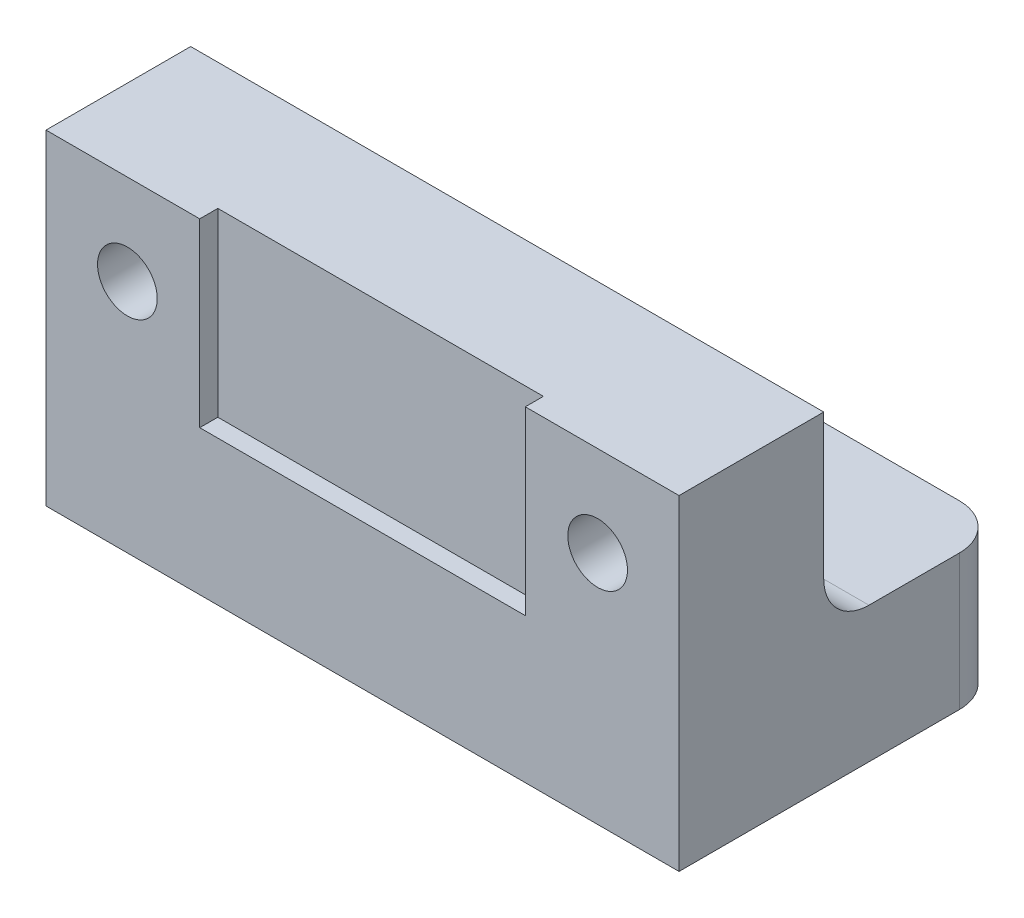
SolidWorks part; units mm, degrees
ref_plane "Front Plane" through (0, 0, 0) normal (0, 0, 1) x (1, 0, 0)
ref_plane "Top Plane" through (0, 0, 0) normal (0, 1, 0) x (1, 0, 0)
ref_plane "Right Plane" through (0, 0, 0) normal (1, 0, 0) x (0, 0, -1)
sketch "Sketch1" plane through (0, 0, 0) normal (0, 0, 1) x (1, 0, 0)
  line L1 (-17.5, -9) -> (17.5, -9)
  line L2 (-17.5, -9) -> (-17.5, 9)
  line L3 (-17.5, 9) -> (17.5, 9)
  line L4 (17.5, -9) -> (17.5, 9)
  line L5 (-17.5, -9) -> (17.5, 9) construction
  line L6 (-17.5, 9) -> (17.5, -9) construction
  point P1 (0, 0)
  dimension "D1" = 35
  dimension "D2" = 18
extrude "Boss-Extrude1" add sketch "Sketch1" along normal blind 8
sketch "Sketch4" plane through (0, 0, 8) normal (0, 0, 1) x (1, 0, 0)
  line L0 (17.5, 9) -> (-17.5, 9) construction
  line L1 (-9, 9) -> (9, 9)
  line L2 (-9, 9) -> (-9, -1)
  line L3 (-9, -1) -> (9, -1)
  line L4 (9, 9) -> (9, -1)
  line L5 (0, 0) -> (0, -1) construction
  dimension "D1" = 10
  dimension "D2" = 18
extrude "Cut-Extrude3" cut sketch "Sketch4" against normal blind 1
sketch "Sketch3" plane through (0, 0, 0) normal (0, 0, -1) x (-1, 0, 0)
  line L0 (-13, 4) -> (13, 4) construction
  line L1 (0, 0) -> (0, 4) construction
  line L3 (-9, 9) -> (9, 9) construction
  circle A0 centre (-13, 4) radius 1.65
  circle A1 centre (13, 4) radius 1.65
  dimension "D1" = 26
  dimension "D3" = 3.3
  dimension "D2" = 5
extrude "Cut-Extrude2" cut sketch "Sketch3" against normal up to next
sketch "Sketch5" plane through (0, 0, 0) normal (0, 0, -1) x (-1, 0, 0)
  circle A0 centre (-13, 4) radius 3
  circle A1 centre (13, 4) radius 3
  dimension "D1" = 6
  dimension "D2" = 6
extrude "Cut-Extrude4" cut sketch "Sketch5" against normal blind 4
sketch "Sketch6" plane through (0, 0, 0) normal (0, 0, 1) x (1, 0, 0)
  line L0 (-17.5, 9) -> (-17.5, -9) construction
  line L1 (17.5, -9) -> (-17.5, -9)
  line L2 (17.5, -9) -> (17.5, -1.5)
  line L3 (17.5, -1.5) -> (-17.5, -1.5)
  line L4 (-17.5, -9) -> (-17.5, -1.5)
  dimension "D1" = 7.5
extrude "Boss-Extrude2" add sketch "Sketch6" against normal blind 10
sketch "Sketch7" plane through (0, -9, 0) normal (0, -1, 0) x (-1, 0, 0)
  line L0 (0, 1) -> (0, 0) construction
  circle A0 centre (0, 1) radius 8
  dimension "D1" = 16
  dimension "D2" = 1
extrude "Cut-Extrude5" cut sketch "Sketch7" against normal blind 4.8 contours A0
fillet "Fillet1" radius 2.5 3 edges at (0, -1.5, 0) (-17.5, -5.25, -10) (17.5, -5.25, -10)
